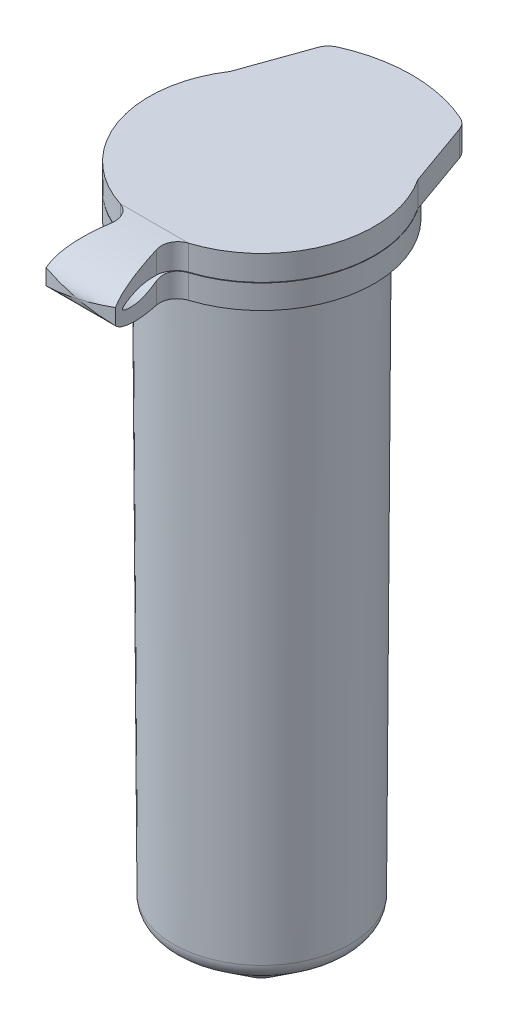
SolidWorks part; units mm, degrees
ref_plane "Front Plane" through (0, 0, 0) normal (0, 0, 1) x (1, 0, 0)
ref_plane "Top Plane" through (0, 0, 0) normal (0, 1, 0) x (1, 0, 0)
ref_plane "Right Plane" through (0, 0, 0) normal (1, 0, 0) x (0, 0, -1)
sketch "Sketch1" plane through (0, 0, 0) normal (0, 0, 1) x (1, 0, 0)
  line L0 (0, 0) -> (0, 36.0603) construction
  line L1 (1.1922, -3.4621) -> (4.774, -0.8029)
  line L2 (5.1779, -0.0058) -> (5.375, 34.2437)
  line L3 (4.1779, 0) -> (4.3787, 34.8937)
  line L4 (0.5961, -2.6592) -> (4.1779, 0)
  line L5 (5.1287, 35.6437) -> (6.6, 35.6437)
  line L6 (6.6, 35.6437) -> (6.6, 34.2437)
  line L7 (6.6, 34.2437) -> (5.375, 34.2437)
  line L8 (5.1779, -0.0058) -> (5.406, 39.6217) construction
  line L9 (4.1779, 0) -> (4.406, 39.6274) construction
  line L10 (4.3787, 34.8937) -> (5.1287, 35.6437)
  line L11 (0, -3.8563) -> (0, -2.8563)
  line L12 (4.25, 32.8937) -> (4.25, 36.3937)
  line L13 (4.25, 36.3937) -> (6, 36.3937)
  line L14 (6.6, 36.1404) -> (6.6, 37.1437)
  line L15 (6.6, 37.1437) -> (0, 37.1437)
  line L16 (0, 37.1437) -> (0, 36.3937)
  line L17 (0, 36.3937) -> (3.65, 36.3937)
  line L18 (3.65, 36.3937) -> (3.65, 32.8937)
  line L19 (3.65, 32.8937) -> (4.25, 32.8937)
  line L20 (6.6, 36.1404) -> (6.6, 35.6737)
  line L21 (6.6, 35.6737) -> (6, 35.6737)
  line L22 (6, 35.6737) -> (6, 36.3937)
  arc A0 (1.1922, -3.4621) -> (0, -3.8563) centre (0, -1.8563) cw
  arc A1 (4.774, -0.8029) -> (5.1779, -0.0058) centre (4.1779, 0) ccw
  arc A2 (4.1779, 0) -> (4.1779, 0) centre (4.1779, 0) ccw
  arc A3 (0.5961, -2.6592) -> (0, -2.8563) centre (0, -1.8563) cw
  point P9 (0, -2.3188)
  point P10 (0.6278, -3.7552)
  point P13 (5.175, -0.5052)
  dimension "D3" = 2
  dimension "D5" = 1
  dimension "D1" = 5.175
  dimension "D2" = 1.4
  dimension "D4" = 3.25
  dimension "D7" = 5.375
  dimension "D8" = 39.5
  dimension "D10" = 135
  dimension "D11" = 0.75
  dimension "D12" = 4.25
  dimension "D13" = 41
  dimension "D14" = 1.47
  dimension "D15" = 6.6
  dimension "D16" = 0.6
  dimension "D17" = 3.5
  dimension "D18" = 0.72
  dimension "D19" = 0.6
  dimension "D6" = 1
revolve "Revolve1" add sketch "Sketch1" angle 360 about L0
sketch "Sketch2" plane through (0, 37.1437, 0) normal (0, 1, 0) x (1, 0, 0)
  line L0 (-5.5, 3.6483) -> (-4.148, 7.4461)
  line L1 (0, -55) -> (0, 55) construction
  line L2 (5.5, 3.6483) -> (4.148, 7.4461)
  circle A0 centre (0, 0) radius 6.6 construction
  arc A1 (5.5, 3.6483) -> (-5.5, 3.6483) centre (0, 0) ccw
  arc A2 (3.6169, 8.0223) -> (-3.6169, 8.0223) centre (0, 0) ccw
  arc A3 (4.148, 7.4461) -> (3.6169, 8.0223) centre (3.2059, 7.1107) ccw
  arc A4 (-4.148, 7.4461) -> (-3.6169, 8.0223) centre (-3.2059, 7.1107) cw
  point P10 (0, -8.8)
  point P11 (0, 8.8)
  point P12 (0, -6.6)
  point P13 (4.0102, 7.8332)
  point P16 (-4.0102, 7.8332)
  dimension "D4" = 1
  dimension "D1" = 11
  dimension "D2" = 8.0203
  dimension "D3" = 15.4
extrude "Boss-Extrude1" add sketch "Sketch2" against normal up to surface (1.47 mm away) up to face at (0, 35.6737, -6.6)
sketch "Sketch3" plane through (0, 37.1437, 0) normal (0, 1, 0) x (1, 0, 0)
  line L1 (2.03, -10.6075) -> (3.0596, -15.9873) construction
  line L2 (0, -10.8) -> (0, -6.6)
  arc A0 (-5.5, 3.6483) -> (5.5, 3.6483) centre (0, 0) ccw construction
  arc A1 (-2.0009, -6.2894) -> (2.0009, -6.2894) centre (0, 0) ccw
  arc A2 (2.0009, -6.2894) -> (1.335, -7.4893) centre (2.304, -7.2423) ccw
  arc A3 (-2.03, -10.6075) -> (2.03, -10.6075) centre (0, 0) ccw
  arc A4 (2.03, -10.6075) -> (1.335, -7.4893) centre (-49.9111, -20.5477) ccw
  arc A5 (3.6169, 8.0223) -> (-3.6169, 8.0223) centre (0, 0) ccw construction
  arc A6 (-2.03, -10.6075) -> (-1.335, -7.4893) centre (49.9111, -20.5477) cw
  arc A7 (-2.0009, -6.2894) -> (-1.335, -7.4893) centre (-2.304, -7.2423) cw
  point P11 (0, 8.8)
  arc M7 (-5.5, 3.6483) -> (5.5, 3.6483) centre (0, 0) ccw
  dimension "D1" = 2
  dimension "D2" = 1.335
  dimension "D3" = 2.03
  dimension "D4" = 19.6
extrude "Boss-Extrude2" add sketch "Sketch3" against normal up to surface (2.9 mm away) contours A3 A4 A2 L2 M7 | A7 A6 A3 L2 M7 region at (-0.8329, 37.1437, 8.795) region at (0.8329, 37.1437, 8.795) up to face at (0, 34.2437, -6.6)
sketch "Sketch5" plane through (0, 0, 0) normal (1, 0, 0) x (0, 0, -1)
  line L0 (-6.2894, 35.6437) -> (-6.6, 35.6437) construction
  line L1 (-6.6, 35.6737) -> (-6.2894, 35.6737) construction
  line L2 (-6.2894, 35.6437) -> (-6.6, 35.6437)
  line L3 (-6.6, 35.6737) -> (-6.2894, 35.6737)
  line L4 (-6.2894, 35.6737) -> (-6.2894, 35.6437)
  line L5 (-6.2894, 34.2437) -> (6.6, 34.2437) construction
  line L8 (3.6483, 37.1437) -> (-6.2894, 37.1437) construction
  line L9 (-6.2894, 34.2437) -> (-6.2894, 33.5334)
  line L10 (-6.2894, 33.5334) -> (-11.4674, 33.8255)
  line L11 (-11.4674, 33.8255) -> (-11.3579, 38.5445)
  line L12 (-11.3579, 38.5445) -> (-6.2894, 38.0355)
  line L13 (-6.2894, 38.0355) -> (-6.2894, 37.1437)
  spline S0 degree 3 poles (-6.6, 35.6737) (-7.519, 35.6737) (-8.4218, 36.3271) (-10.3699, 35.6587) (-8.4216, 34.9903) (-7.5213, 35.6437) (-6.6, 35.6437) knots 0 0 0 0 0.417766 0.5 0.582234 1 1 1 1
  spline S1 degree 3 poles (-6.2894, 37.1437) (-9.4319, 37.1437) (-12.1354, 35.4791) (-9.4967, 34.2437) (-6.2894, 34.2437) knots 0 0 0 0 0.503822 1 1 1 1
  point P5 (-6.2894, 35.6587)
  dimension "D1" = 0.25
  dimension "D2" = 0.25
extrude "Cut-Extrude1" cut sketch "Sketch5" against normal through all and the other way through all
